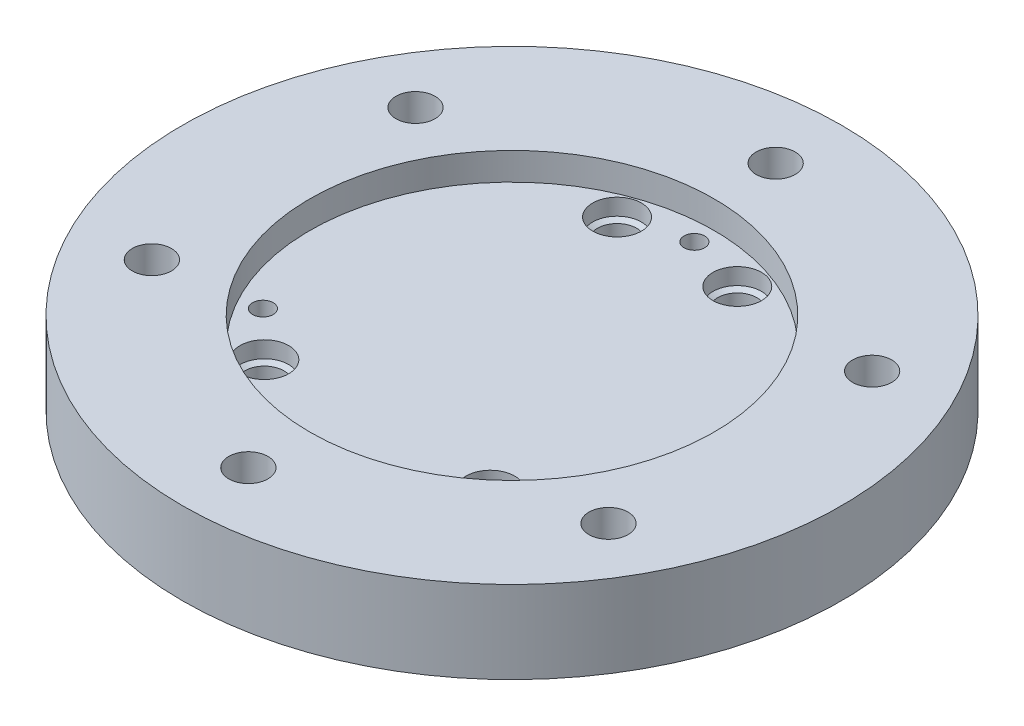
SolidWorks part; units mm, degrees
ref_plane "Front Plane" through (0, 0, 0) normal (0, 0, 1) x (1, 0, 0)
ref_plane "Top Plane" through (0, 0, 0) normal (0, 1, 0) x (1, 0, 0)
ref_plane "Right Plane" through (0, 0, 0) normal (1, 0, 0) x (0, 0, -1)
ref_axis "Y Axis" through (0, 0.1588, 0) along (0, -1, 0)
sketch "outer" plane through (0, 0, 0) normal (0, 1, 0) x (1, 0, 0)
  circle A0 centre (0, 0) radius 19.05
  dimension "D1" = 38.1
extrude "Body" add sketch "outer" against normal blind 4.7625
sketch "inner" plane through (0, 0, 0) normal (0, 1, 0) x (1, 0, 0)
  circle A0 centre (0, 0) radius 11.684
  dimension "D1" = 23.368
extrude "Pocket" cut sketch "inner" against normal blind 1.5875
sketch "Screw Position" plane through (0, 0, 0) normal (0, 1, 0) x (1, 0, 0)
  point P0 (0, -15.24)
  dimension "D1" = 15.24
hole_wizard "#4-40 Tapped Hole3" positions "Sketch12" profile "Sketch13" tap size "#4-40" standard "ANSI Inch" end condition through all
sketch "Sketch12" plane through (0, 0, 0) normal (0, 1, 0) x (1, 0, 0)
  point P0 (0, -15.24)
sketch "Sketch13" plane through (0, 0, 15.24) normal (1, 0, 0) x (0, 0, 1)
  line L0 (0, 0) -> (0, 4.7625)
  line L1 (0, 4.7625) -> (1.1303, 4.7625)
  line L2 (1.1303, 4.7625) -> (1.1303, 0)
  line L5 (1.1303, 0) -> (0, 0)
  line L11 (0, -6.35) -> (0, 107.95) construction
  dimension "Thru Tap Drill Dia." = 2.2606
  dimension "Thru Tap Drill Depth" = 4.7625
cosmetic thread "Hole Thread3" parameters "D2"=2.8448
pattern_circular "Screw Holes" count 6 over 360 about axis through (0, 0.1588, 0) along (0, -1, 0) of "#4-40 Tapped Hole3"
sketch "Inner Screw Position" plane through (0, 0, 0) normal (0, 1, 0) x (1, 0, 0)
  point P0 (0, 10.541)
  dimension "D1" = 10.541
hole_wizard "#0-80 Tapped Hole1" positions "Sketch16" profile "Sketch17" tap size "#0-80" standard "ANSI Inch" end condition through all
sketch "Sketch16" plane through (0, -1.5875, 0) normal (0, 1, 0) x (1, 0, 0)
  point P0 (0, 10.541)
sketch "Sketch17" plane through (0, -1.5875, -10.541) normal (1, 0, 0) x (0, 0, 1)
  line L0 (0, 0) -> (0, 3.175)
  line L1 (0, 3.175) -> (0.5956, 3.175)
  line L2 (0.5956, 3.175) -> (0.5956, 0)
  line L5 (0.5956, 0) -> (0, 0)
  line L11 (0, -6.35) -> (0, 107.95) construction
  dimension "Thru Tap Drill Dia." = 1.1913
  dimension "Thru Tap Drill Depth" = 3.175
cosmetic thread "Hole Thread4" parameters "D2"=1.524
pattern_circular "Inner Screw Holes" count 3 over 360 about axis through (0, 0.1588, 0) along (0, -1, 0) of "#0-80 Tapped Hole1"
sketch "IO Postion" plane through (0, 0, 0) normal (0, 1, 0) x (1, 0, 0)
  line L0 (0, 0) -> (-3.4749, 9.5473) construction
  line L1 (0, 0) -> (-5.9719, 8.2196) construction
  point P0 (-3.4749, 9.5473)
  point P1 (0, 0)
  point P5 (-5.9719, 8.2196)
  point P6 (-8.0062, 6.2551)
  point P7 (-9.4202, 3.806)
  point P8 (-10.1043, 1.062)
  point P9 (-10.0056, -1.7643)
  point P13 (10.0056, -1.7643)
  point P14 (10.1043, 1.062)
  point P15 (9.4202, 3.806)
  point P16 (8.0062, 6.2551)
  point P17 (5.9719, 8.2196)
  point P18 (3.4749, 9.5473)
  point P19 (-6.5307, -7.783)
  point P20 (-4.1324, -9.2816)
  point P21 (-1.414, -10.0611)
  point P22 (1.414, -10.0611)
  point P23 (4.1324, -9.2816)
  point P24 (6.5307, -7.783)
  point P25 (0, 0)
  dimension "D3" = 16
  dimension "D2" = 6
  dimension "D4" = 3
hole_wizard "#43 (0.089) Diameter Hole1" positions "Sketch20" profile "Sketch21" hole size "#43" standard "ANSI Inch" end condition through all
sketch "Sketch20" plane through (0, -1.5875, 0) normal (0, 1, 0) x (1, 0, 0)
  point P0 (-3.4749, 9.5473)
sketch "Sketch21" plane through (-3.4749, -1.5875, -9.5473) normal (1, 0, 0) x (0, 0, 1)
  line L0 (0, 0) -> (0, 3.175)
  line L1 (0, 3.175) -> (1.1303, 3.175)
  line L2 (1.1303, 3.175) -> (1.1303, 0)
  line L5 (1.1303, 0) -> (0, 0)
  line L11 (0, -6.35) -> (0, 107.95) construction
  dimension "Thru Hole Dia." = 2.2606
  dimension "Thru Hole Depth" = 3.175
hole_wizard "#34 (0.111) Diameter Hole1" positions "Sketch22" profile "Sketch23" hole size "#34" standard "ANSI Inch"
sketch "Sketch22" plane through (0, -1.5875, 0) normal (0, 1, 0) x (1, 0, 0)
  point P0 (-3.4749, 9.5473)
sketch "Sketch23" plane through (-3.4749, -1.5875, -9.5473) normal (1, 0, 0) x (0, 0, 1)
  line L0 (0, 0) -> (0, 1.7995)
  line L1 (0, 1.7995) -> (1.4097, 0.9525)
  line L2 (1.4097, 0.9525) -> (1.4097, 0)
  line L5 (1.4097, 0) -> (0, 0)
  line L10 (0, 1.7995) -> (-1.4097, 0.9525) construction
  line L11 (0, -6.35) -> (0, 107.95) construction
  dimension "Hole Dia." = 2.8194
  dimension "Hole Depth" = 0.9525
  dimension "Drill Angle" = 118
hole_wizard "#34 (0.111) Diameter Hole2" positions "Sketch28" profile "Sketch27" hole size "#34" standard "ANSI Inch"
sketch "Sketch28" plane through (0, -4.7625, 0) normal (0, -1, 0) x (-1, 0, 0)
  point P0 (3.4749, 9.5473)
sketch "Sketch27" plane through (-3.4749, -4.7625, -9.5473) normal (1, 0, 0) x (0, 0, -1)
  line L0 (0, 0) -> (0, 1.7995)
  line L1 (0, 1.7995) -> (1.4097, 0.9525)
  line L2 (1.4097, 0.9525) -> (1.4097, 0)
  line L5 (1.4097, 0) -> (0, 0)
  line L10 (0, 1.7995) -> (-1.4097, 0.9525) construction
  line L11 (0, -6.35) -> (0, 107.95) construction
  dimension "Hole Dia." = 2.8194
  dimension "Hole Depth" = 0.9525
  dimension "Drill Angle" = 118
sketch "IO Hole Position" plane through (0, 0, 0) normal (0, 1, 0) x (1, 0, 0)
  point P0 (3.4749, 9.5473)
  point P1 (-6.5307, -7.783)
  point P3 (6.5307, -7.783)
pattern_sketch "IO Holes Pattern" of "#43 (0.089) Diameter Hole1", "#34 (0.111) Diameter Hole1", "#34 (0.111) Diameter Hole2" driven by "IO Hole Position"
equation "\"outer_d\"= 3 / 2in"
equation "\"screw_r\"= 0.6in"
equation "\"inner_d\" = 0.920in"
equation "\"bottom_h\" = 3 / 16in"
equation "\"pocket_h\"= 1 / 16in"
equation "\"screw_inner_r\"= 0.415in"
equation "\"io_r\"= 0.4in"
equation "\"D1@outer\" = \"outer_d\""
equation "\"D1@Body\" = \"bottom_h\""
equation "\"D1@inner\" = \"inner_d\""
equation "\"D1@Pocket\"=\"pocket_h\""
equation "\"D1@Screw Position\" = \"screw_r\""
equation "\"D1@Inner Screw Position\" = \"screw_inner_r\""
equation "\"D1@IO Postion\" = \"io_r\""
